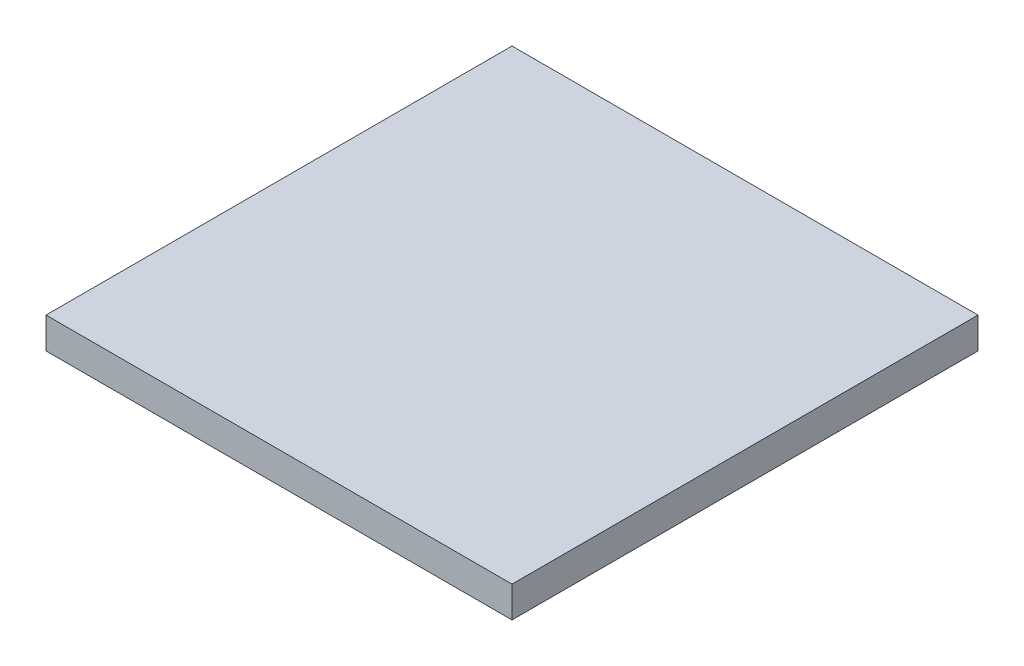
SolidWorks part; units mm, degrees
ref_plane "Front Plane" through (0, 0, 0) normal (0, 0, 1) x (1, 0, 0)
ref_plane "Top Plane" through (0, 0, 0) normal (0, 1, 0) x (1, 0, 0)
ref_plane "Right Plane" through (0, 0, 0) normal (1, 0, 0) x (0, 0, -1)
sketch "Sketch2" plane through (0, 0, 0) normal (0, 1, 0) x (1, 0, 0)
  line L0 (0, -15) -> (0, 15)
  line L21 (0, -47.4) -> (0, 0) construction
  line L22 (0, 0) -> (0, 47.4) construction
  line L24 (-15, 15) -> (15, 15)
  line L25 (-15, 15) -> (-15, -15)
  line L26 (-15, -15) -> (15, -15)
  line L27 (15, 15) -> (15, -15)
  point P2 (0, 0)
  point P22 (0, 0)
  dimension "D4" = 30
extrude "Boss-Extrude1" add sketch "Sketch2" along normal blind 2 contours L24 L27 L26 L25
sketch "Sketch3" plane through (0, 2, 0) normal (0, 1, 0) x (1, 0, 0)
  line L0 (-5, 15) -> (-5, -15) construction
  line L1 (-15, 15) -> (15, 15) construction
  line L2 (-15, -15) -> (15, -15) construction
  line L3 (-15, 15) -> (-15, -15) construction
  point P8 (-5, 0)
  point P9 (0, 0)
  dimension "D1" = 10
sketch "Sketch12" plane through (0, 2, 0) normal (0, 1, 0) x (1, 0, 0)
  line L0 (19.0856, 0) -> (-6.6753, 15) construction
  line L1 (19.0856, 0) -> (-6.6753, -15) construction
  line L2 (-1.7286, 12.1196) -> (-5, 0) construction
  line L3 (-5, 0) -> (-1.7286, -12.1196) construction
  line L4 (-15, 15) -> (15, 15) construction
  line L5 (-15, -15) -> (15, -15) construction
  line L6 (-5.1673, 6.0659) -> (-4.2802, 5.8441)
  line L7 (-5, 0) -> (-5.9144, 0)
  line L8 (-4.2802, -5.8441) -> (-5.1673, -6.0659)
  line L9 (-15, 15) -> (-15, -15) construction
  line L10 (15, 15) -> (15, -15) construction
  line L11 (-15, 0) -> (15, 0) construction
  line L12 (-0.8644, 11.6164) -> (-1.7286, 12.1196)
  line L13 (-2.5188, 12.5797) -> (-3.383, 13.0829)
  line L14 (-0.8644, -11.6164) -> (-1.7286, -12.1196)
  line L15 (-2.5188, -12.5797) -> (-3.383, -13.0829)
  arc A0 (-0.8644, 11.6164) -> (-0.8644, -11.6164) centre (19.0856, 0) ccw
  arc A1 (-3.383, 13.0829) -> (-3.383, -13.0829) centre (19.0856, 0) ccw
  arc A2 (-2.5188, -12.5797) -> (-2.5188, 12.5797) centre (19.0856, 0) cw
  arc A3 (-1.7286, -12.1196) -> (-1.7286, 12.1196) centre (19.0856, 0) cw
  circle A4 centre (-4.7238, 5.955) radius 0.4572
  circle A5 centre (-5.4572, 0) radius 0.4572
  circle A6 centre (-4.7238, -5.955) radius 0.4572
  point P11 (-5, 0)
  point P29 (-15, 0)
  point P30 (15, 0)
  dimension "D1" = 25
  dimension "D3" = 1
  dimension "D4" = 1
  dimension "D5" = 0.9144
  dimension "D6" = 0.9144
  dimension "D7" = 0.9144
  dimension "D8" = 0.9144
  dimension "D9" = 6
  dimension "D10" = 6
  dimension "D2" = 25.4
ref_plane "Plane1" through (0, 0, 0) normal (0, 0, 1) x (1, 0, 0)
sketch "Sketch13" plane through (0, 0, 0) normal (0, 0, 1) x (1, 0, 0)
  line L0 (-5, 2) -> (-15, 12)
  line L1 (-15, 2) -> (15, 2) construction
  point P5 (-15, 11.9869)
  dimension "D1" = 45
  dimension "D2" = 10
equation "\"mountWallThickness\"= 1.00mm"
equation "\"arcLength\"= 25.4000mm"
equation "\"tapeSpringThickness\"= 0.9144mm"
equation "\"curvatureRadius\"= 25.000mm"
equation "\"distanceBetweenWires\"= 7mm"
equation "\"D1@Sketch12\"=\"curvatureRadius\""
equation "\"D2@Sketch12\"=\"arcLength\""
equation "\"D3@Sketch12\"=\"mountWallThickness\""
equation "\"D4@Sketch12\"=\"mountWallThickness\""
equation "\"D5@Sketch12\"=\"tapeSpringThickness\""
equation "\"D6@Sketch12\"=\"tapeSpringThickness\""
equation "\"D7@Sketch12\"=\"tapeSpringThickness\""
equation "\"D8@Sketch12\"=\"tapeSpringThickness\""
equation "\"D9@Sketch12\"=6mm"
